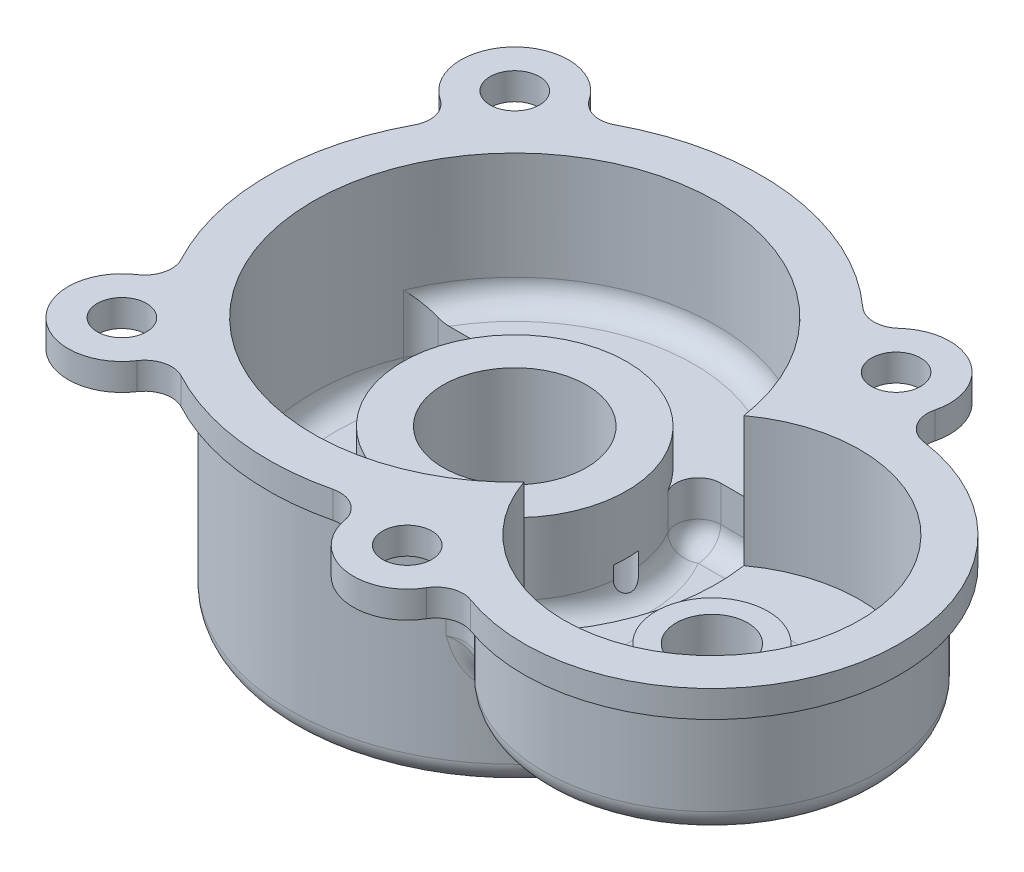
SolidWorks part; units mm, degrees
ref_plane "Front Plane" through (0, 0, 0) normal (0, 0, 1) x (1, 0, 0)
ref_plane "Top Plane" through (0, 0, 0) normal (0, 1, 0) x (1, 0, 0)
ref_plane "Right Plane" through (0, 0, 0) normal (1, 0, 0) x (0, 0, -1)
sketch "Sketch1" plane through (0, 0, 0) normal (0, 1, 0) x (1, 0, 0)
  line L0 (-43.8406, 43.8406) -> (0, 0) construction
  line L1 (-87.3503, 0) -> (74.0989, 0) construction
  line L2 (0, 0) -> (-43.8406, -43.8406) construction
  circle A0 centre (0, 0) radius 50
  circle A1 centre (0, 0) radius 45
  arc A2 (34.9855, -35.7213) -> (49.0999, 9.4446) centre (64, -20) ccw
  arc A3 (34.7594, -43.4784) -> (53.3308, 15.9502) centre (64, -20) ccw
  circle A5 centre (32, -56) radius 5.5
  circle A6 centre (53.1037, 32) radius 5.5
  arc A10 (50.0588, 36.5803) -> (35.4878, -50.8391) centre (0, 0) ccw construction
  circle A11 centre (-43.8406, 43.8406) radius 5.5
  arc A12 (-33.8279, 50.4547) -> (-50.4547, 33.8279) centre (-43.8406, 43.8406) ccw
  arc A13 (-33.8279, 50.4547) -> (-25.9866, 48.4736) centre (-28.8215, 53.7617) ccw
  arc A14 (-48.4736, 25.9866) -> (-50.4547, 33.8279) centre (-53.7617, 28.8215) ccw
  arc A15 (-48.4736, 25.9866) -> (-48.4736, -25.9866) centre (0, 0) ccw
  arc A17 (64.7315, 29.0344) -> (44.9772, 40.8295) centre (53.1037, 32) ccw
  arc A19 (36.8897, 40.794) -> (-25.9866, 48.4736) centre (0, 0) ccw
  arc A20 (64.7315, 29.0344) -> (69.7272, 21.6077) centre (70.5453, 27.5516) ccw
  arc A21 (36.8897, 40.794) -> (44.9772, 40.8295) centre (40.914, 45.2443) ccw
  arc A22 (46.0926, 19.377) -> (53.3308, 15.9502) centre (51.6238, 21.7023) ccw
  arc A24 (34.7594, -43.4784) -> (26.8579, -42.1741) centre (30.0809, -47.235) ccw
  arc A25 (20.2033, -58.1993) -> (42.358, -62.059) centre (32, -56) ccw
  arc A26 (49.5949, -59.4524) -> (42.358, -62.059) centre (47.537, -65.0885) ccw
  arc A27 (20.2033, -58.1993) -> (12.8979, -53.4663) centre (14.3049, -59.299) ccw
  arc A28 (49.5949, -59.4524) -> (69.7272, 21.6077) centre (64, -20) ccw
  circle A29 centre (-43.8406, -43.8406) radius 5.5
  arc A30 (-50.4547, -33.8279) -> (-33.8279, -50.4547) centre (-43.8406, -43.8406) ccw
  arc A31 (-50.4547, -33.8279) -> (-48.4736, -25.9866) centre (-53.7617, -28.8215) ccw
  arc A32 (-25.9866, -48.4736) -> (-33.8279, -50.4547) centre (-28.8215, -53.7617) ccw
  arc A33 (-25.9866, -48.4736) -> (12.8979, -53.4663) centre (0, 0) ccw
  dimension "D1" = 100
  dimension "D2" = 90
  dimension "D3" = 66
  dimension "D4" = 75
  dimension "D7" = 42
  dimension "D8" = 11
  dimension "D11" = 11
  dimension "D13" = 55
  dimension "D14" = 124
  dimension "D15" = 11
  dimension "D17" = 24
  dimension "D18" = 6
  dimension "D19" = 6
  dimension "D20" = 55
  dimension "D21" = 12
  dimension "D22" = 6
  dimension "D23" = 6
  dimension "D24" = 6
  dimension "D25" = 6
  dimension "D26" = 24
  dimension "D27" = 6
  dimension "D28" = 6
  dimension "D29" = 11
  dimension "D30" = 24
  dimension "D32" = 6
  dimension "D33" = 6
  dimension "D5" = 20
  dimension "D6" = 64
  dimension "D9" = 32
  dimension "D10" = 56
  dimension "D12" = 32
  dimension "D16" = 45
  dimension "D31" = 45
extrude "Boss-Extrude1" add sketch "Sketch1" along normal blind 6 contours A32 A33 A27 A25 A26 A28 A20 A17 A21 A19 A13 A12 A14 A15 A31 A30 A3 A24 A0 A22 A5 A6 A11 A29 region at (-30.7904, 0, -45.9687)
sketch "Sketch2" plane through (0, 6, 0) normal (0, 1, 0) x (1, 0, 0)
  circle A0 centre (0, 0) radius 45
  arc A1 (34.9855, -35.7213) -> (49.0999, 9.4446) centre (64, -20) ccw
  circle A2 centre (0, 0) radius 50
  dimension "D1" = 90
  dimension "D2" = 66
  dimension "D5" = 100
  dimension "D3" = 20
  dimension "D4" = 64
extrude "Boss-Extrude2" add sketch "Sketch2" against normal blind 56 contours A2
sketch "Sketch3" plane through (0, 6, 0) normal (0, 1, 0) x (1, 0, 0)
  circle A0 centre (0, 0) radius 45
  dimension "D1" = 90
extrude "Cut-Extrude1" cut sketch "Sketch3" against normal blind 42
sketch "Sketch4" plane through (0, 6, 0) normal (0, 1, 0) x (1, 0, 0)
  arc A0 (26.8579, -42.1741) -> (46.0926, 19.377) centre (0, 0) ccw
  arc A2 (34.7594, -43.4784) -> (53.3308, 15.9502) centre (64, -20) ccw
  arc A3 (46.0926, 19.377) -> (53.3308, 15.9502) centre (51.6238, 21.7023) ccw
  arc A4 (34.7594, -43.4784) -> (26.8579, -42.1741) centre (30.0809, -47.235) ccw
  dimension "D4" = 100
  dimension "D5" = 12
  dimension "D6" = 37.5
  dimension "D7" = 12
  dimension "D2" = 20
  dimension "D3" = 64
extrude "Boss-Extrude3" add sketch "Sketch4" against normal blind 32
sketch "Sketch20" plane through (0, 6, 0) normal (0, 1, 0) x (1, 0, 0)
  arc A1 (32.8148, -30.7927) -> (44.5091, 6.629) centre (64, -20) ccw
  arc A2 (32.8148, -30.7927) -> (44.5091, 6.629) centre (0, 0) ccw
  dimension "D2" = 66
  dimension "D5" = 90
  dimension "D3" = 64
  dimension "D4" = 20
extrude "Cut-Extrude2" cut sketch "Sketch20" against normal blind 29
sketch "Sketch21" plane through (0, -36, 0) normal (0, 1, 0) x (1, 0, 0)
  circle A0 centre (0, 0) radius 25
  circle A1 centre (0, 0) radius 16
  dimension "D1" = 50
  dimension "D2" = 32
extrude "Boss-Extrude4" add sketch "Sketch21" along normal blind 21
sketch "Sketch22" plane through (0, -36, 0) normal (0, 1, 0) x (1, 0, 0)
  line L0 (-37.081, 20) -> (-25.9808, 20)
  line L2 (0, 84.8852) -> (0, -63.7062) construction
  line L3 (25.9808, 20) -> (37.081, 20)
  arc A0 (41.7161, 16.875) -> (-41.7161, 16.875) centre (0, 0) ccw
  arc A2 (21.6506, 12.5) -> (-21.6506, 12.5) centre (0, 0) ccw
  arc A4 (-21.6506, 12.5) -> (-25.9808, 20) centre (-25.9808, 15) ccw
  arc A5 (-37.081, 20) -> (-41.7161, 16.875) centre (-37.081, 15) ccw
  arc A6 (21.6506, 12.5) -> (25.9808, 20) centre (25.9808, 15) cw
  arc A7 (37.081, 20) -> (41.7161, 16.875) centre (37.081, 15) cw
  dimension "D1" = 90
  dimension "D2" = 50
  dimension "D3" = 5
  dimension "D5" = 10
  dimension "D4" = 20
extrude "Boss-Extrude5" add sketch "Sketch22" along normal blind 13
sketch "Sketch24" plane through (0, -50, 0) normal (0, -1, 0) x (1, 0, 0)
  circle A0 centre (0, 0) radius 32
  dimension "D1" = 64
extrude "Boss-Extrude6" add sketch "Sketch24" along normal blind 3
sketch "Sketch25" plane through (0, -53, 0) normal (0, -1, 0) x (1, 0, 0)
  line L0 (-73.2573, 0) -> (117.7445, 0) construction
  arc A0 (20.5455, 7.8667) -> (20.5455, -7.8667) centre (0, 0) ccw
  arc A1 (20.5455, -7.8667) -> (20.5455, 7.8667) centre (22, 0) ccw
  dimension "D1" = 44
  dimension "D2" = 16
  dimension "D3" = 22
extrude "Cut-Extrude3" cut sketch "Sketch25" against normal blind 13
sketch "Sketch26" plane through (0, -40, 0) normal (0, -1, 0) x (1, 0, 0)
  circle A0 centre (22, 0) radius 4
  dimension "D1" = 8
extrude "Cut-Extrude4" cut sketch "Sketch26" against normal blind 12
sketch "Sketch27" plane through (0, -40, 0) normal (0, -1, 0) x (1, 0, 0)
  circle A0 centre (0, 0) radius 16
  dimension "D1" = 32
extrude "Cut-Extrude5" cut sketch "Sketch27" against normal through all
sketch "Sketch29" plane through (0, -53, 0) normal (0, -1, 0) x (1, 0, 0)
  line L0 (-43.3013, -25) -> (43.3013, -25)
  arc A0 (-43.3013, -25) -> (43.3013, -25) centre (0, 0) ccw
  dimension "D1" = 100
  dimension "D2" = 25
extrude "Cut-Extrude6" cut sketch "Sketch29" against normal blind 27
sketch "Sketch30" plane through (0, -23, 0) normal (0, 1, 0) x (1, 0, 0)
  circle A0 centre (64, -20) radius 12.5
  dimension "D1" = 25
  dimension "D2" = 64
  dimension "D3" = 20
extrude "Boss-Extrude7" add sketch "Sketch30" along normal blind 8
sketch "Sketch31" plane through (0, -15, 0) normal (0, 1, 0) x (1, 0, 0)
  circle A0 centre (64, -20) radius 8
  dimension "D1" = 16
extrude "Cut-Extrude7" cut sketch "Sketch31" against normal through all
fillet "Fillet1" radius 5 1 edges at (0, -50, 50)
fillet "Fillet2" radius 3 4 edges at (49.0563, 0, -16.2793) (99.793, 0, 31.1853) (31.0581, 0, 41.3151) (-47.724, 0, -14.9137)
fillet "Fillet3" radius 5 3 edges at (31.0581, -26, 41.3151) (49.0563, -26, -16.2793) (99.793, -26, 31.1853)
fillet "Fillet4" radius 5 3 edges at (48.1412, -25.5399, -13.5065) (31.8846, -25.5399, 38.5146) (47.724, -26, 14.9137)
fillet "Fillet5" radius 5 1 edges at (0, -23, -45)
fillet "Fillet6" radius 5 8 edges at (-21.6506, -36, -17.5) (-31.5309, -36, -20) (-39.8761, -36, -19.1458) (23.7447, -36, -7.8223) (21.6506, -36, -17.5) (31.5309, -36, -20) (39.8761, -36, -19.1458) (0, -36, 45)
fillet "Fillet7" radius 5 1 edges at (64, -23, 32.5)
fillet "Fillet8" radius 5 1 edges at (0, -26, -25)
